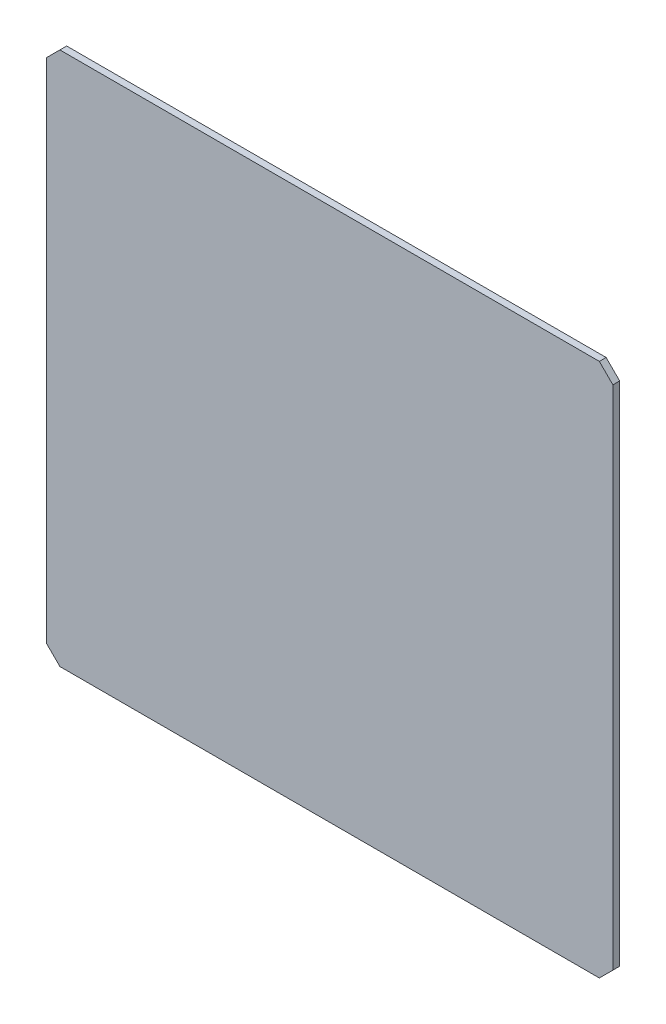
SolidWorks part; units mm, degrees
material "Acrilico (impatto medio-alto)"
ref_plane "Piano frontale" through (0, 0, 0) normal (0, 0, 1) x (1, 0, 0)
ref_plane "Piano superiore" through (0, 0, 0) normal (0, 1, 0) x (1, 0, 0)
ref_plane "Piano destro" through (0, 0, 0) normal (1, 0, 0) x (0, 0, -1)
sketch "Schizzo1" plane through (0, 0, 0) normal (0, 0, 1) x (1, 0, 0)
  line L0 (-209, 187) -> (-199, 197)
  line L1 (199, -197) -> (-199, -197)
  line L2 (209, -187) -> (209, 187)
  line L3 (199, 197) -> (-199, 197)
  line L4 (-209, -187) -> (-209, 187)
  line L5 (209, -197) -> (-209, 197) construction
  line L6 (209, 197) -> (-209, -197) construction
  line L7 (209, 187) -> (199, 197)
  line L8 (199, -197) -> (209, -187)
  line L9 (-199, -197) -> (-209, -187)
  point P0 (0, 0)
  dimension "D1" = 418
  dimension "D2" = 394
extrude "Estrusione-Estrusione1" add sketch "Schizzo1" along normal blind 5 contours L4 L0 L3 L7 L2 L8 L1 L9
